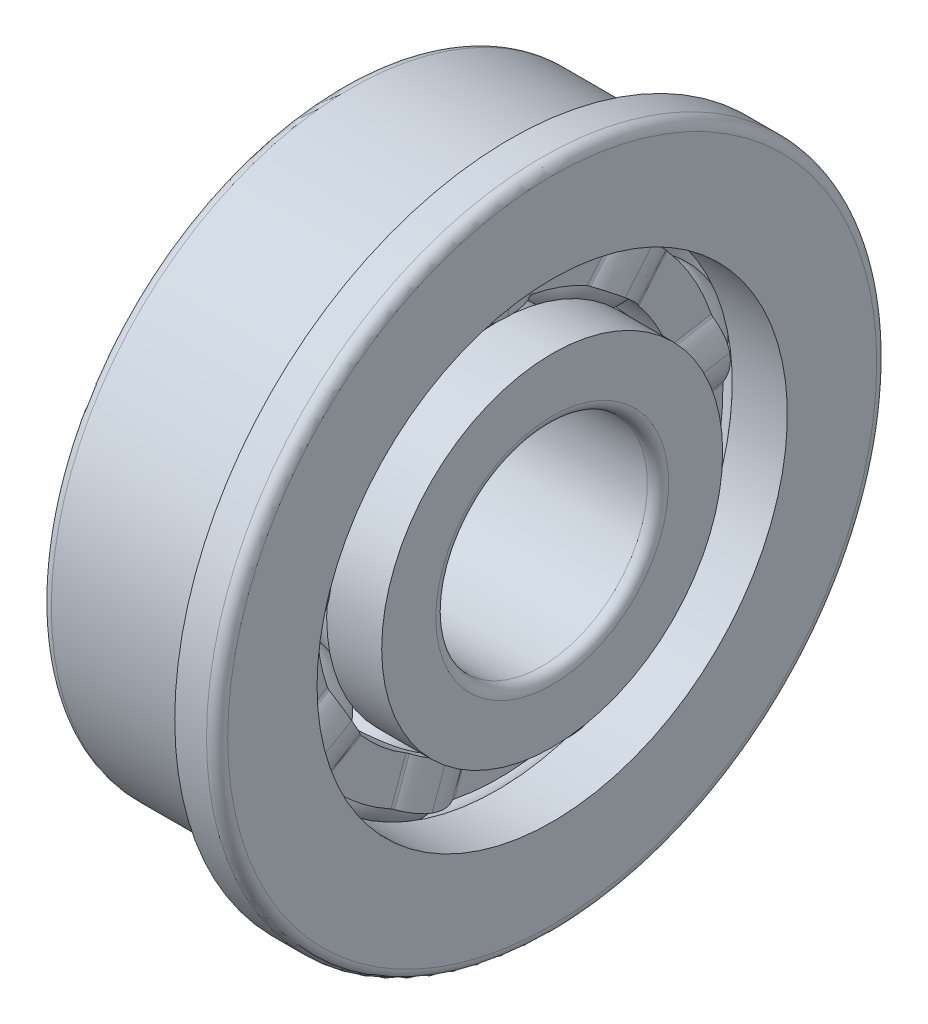
SolidWorks part; units mm, degrees
ref_plane "Front" through (0, 0, 0) normal (0, 0, 1) x (1, 0, 0)
ref_plane "Top" through (0, 0, 0) normal (0, 1, 0) x (1, 0, 0)
ref_plane "Right" through (0, 0, 0) normal (1, 0, 0) x (0, 0, -1)
sketch "Support-Front-Body" plane through (0, 0, 0) normal (0, 0, 1) x (1, 0, 0)
  line L0 (-3, 0) -> (3, 0) construction
  line L1 (3, 0) -> (3, 3) construction
  line L2 (-3, 0) -> (-3, 3) construction
  line L4 (-3, 8.5) -> (3, 8.5)
  line L5 (-3, 8.5) -> (-3, 6.6667)
  line L6 (-3, 6.6667) -> (3, 6.6667)
  line L7 (3, 9.5) -> (3, 6.6667)
  line L8 (-3, 4.8333) -> (3, 4.8333)
  line L9 (-3, 4.8333) -> (-3, 3)
  line L10 (-3, 3) -> (3, 3)
  line L11 (3, 4.8333) -> (3, 3)
  line L13 (-3, 5.75) -> (3, 5.75) construction
  line L14 (0, 0) -> (0, 3) construction
  line L15 (0, 3) -> (0, 4.8333) construction
  line L16 (0, 4.8333) -> (0, 6.6667) construction
  line L17 (0, 6.6667) -> (0, 8.5) construction
  line L19 (1.8, 9.5) -> (3, 9.5)
  line L20 (1.8, 9.5) -> (1.8, 8.5)
  dimension "Diam-Inner" = 6
  dimension "Diam-Outer" = 17
  dimension "CC-Ball" = 11.5
  dimension "Width-Inner" = 6
  dimension "Diam-Flange" = 19
  dimension "Width-Flange" = 1.2
sketch "Support-Front-Ball" plane through (0, 0, 0) normal (0, 0, 1) x (1, 0, 0)
  line L0 (-1.65, 5.75) -> (1.65, 5.75) construction
  line L1 (0, 0) -> (0, 4.1) construction
  line L2 (-3, 5.75) -> (3, 5.75) construction
  line L3 (0, 5.75) -> (0, 7.4) construction
  line L6 (0, 4.1) -> (0, 5.75) construction
  circle A0 centre (0, 5.75) radius 1.65
  dimension "Diam-Ball" = 3.3
sketch "Support-Front-Groove" plane through (0, 0, 0) normal (0, 0, 1) x (1, 0, 0)
  line L0 (0, 6.6667) -> (0, 6.3611) construction
  line L1 (0, 6.3611) -> (0, 6.0556) construction
  line L2 (0, 6.0556) -> (0, 5.75) construction
  line L3 (-3, 5.75) -> (3, 5.75) construction
  line L4 (-1.65, 5.75) -> (1.65, 5.75) construction
  line L6 (-3, 6.6667) -> (3, 6.6667) construction
  line L7 (0, 4.1673) -> (0, 4.1) construction
  line L8 (1.3719, 4.8333) -> (1.4393, 4.8333) construction
  line L9 (-3, 4.8333) -> (3, 4.8333) construction
  line L11 (0, 0) -> (0, 4.1) construction
  line L12 (-1.65, 5.75) -> (1.65, 5.75) construction
  circle A0 centre (0, 5.75) radius 1.65 construction
  circle A1 centre (0, 6.0556) radius 1.8882
  circle A2 centre (0, 5.4444) radius 1.8882
sketch "Support-Front-Ball-Cage" plane through (0, 0, 0) normal (0, 0, 1) x (1, 0, 0)
  line L0 (1.65, 5.75) -> (-1.7681, 5.75) construction
  line L1 (-1.7681, 6.3611) -> (1.7681, 6.3611)
  line L2 (-1.7681, 6.3611) -> (-1.7681, 5.1389)
  line L3 (-1.7681, 5.1389) -> (1.7681, 5.1389)
  line L4 (1.7681, 6.3611) -> (1.7681, 5.1389)
  line L5 (-3, 5.75) -> (3, 5.75) construction
  line L6 (0, 5.1389) -> (0, 6.3611) construction
  line L7 (0, 4.8333) -> (0, 6.6667) construction
  line L8 (1.65, 5.75) -> (1.7681, 5.75) construction
  line L9 (1.709, 5.75) -> (1.709, 6.0556) construction
  line L10 (1.709, 6.0556) -> (1.709, 6.3611) construction
  line L11 (1.709, 6.3611) -> (1.709, 6.6667) construction
  line L12 (-3, 6.6667) -> (3, 6.6667) construction
  line L13 (1.7681, 6.5139) -> (1.4625, 6.5139) construction
  line L14 (0, 6.3611) -> (0, 7.5181) construction
  circle A0 centre (0, 5.75) radius 1.65 construction
  circle A1 centre (0, 5.75) radius 1.7681 construction
  point P26 (1.709, 6.5139)
sketch "Support-Right-Ball-Cage" plane through (0, 0, 0) normal (1, 0, 0) x (0, 0, -1)
  line L0 (0, 0) -> (0, 8.5) construction
  line L1 (0, 0) -> (-5.4637, 6.5114) construction
  line L2 (0, 3.9819) -> (-2.5595, 3.0503) construction
  line L3 (-4.8325, 5.7592) -> (0, 7.5181) construction
  line L4 (0, 0) -> (-3.1968, 7.8759) construction
  line L6 (-2.6137, 8.0882) -> (0, 0) construction
  circle A0 centre (0, 0) radius 5.1389
  circle A1 centre (0, 0) radius 6.3611
  circle A2 centre (0, 5.75) radius 1.7681
  circle A3 centre (0, 0) radius 5.75 construction
  circle A4 centre (-3.696, 4.4048) radius 1.7681
  dimension "Angle-Ball" = 40
ref_plane "Ref-Plane-1" through (0, 3.5161, 1.2798) normal (0, 0.9397, 0.342) x (-1, 0, 0)
sketch "Support-Ball-Gage-Inner" plane through (0, 3.5161, 1.2798) normal (0, 0.9397, 0.342) x (-1, 0, 0)
  line L0 (-1.4787, -0.3427) -> (-1.4787, 0.3427)
  line L1 (1.4787, -0.3427) -> (1.4787, 0.3427)
  line L2 (1.7681, 1.3619) -> (1.7681, -1.3619)
  line L3 (-1.7681, 0) -> (-1.4787, 0) construction
  line L4 (-1.65, -1.9666) -> (-1.65, -0.3427) construction
  line L5 (-1.65, -0.3427) -> (-1.4787, -0.3427) construction
  line L6 (-1.65, -0.3427) -> (-1.65, -0.1713) construction
  line L7 (-1.65, -0.1713) -> (-1.65, 0) construction
  line L8 (-1.4787, 0) -> (0, 0) construction
  line L9 (-1.7681, 1.3619) -> (-1.7681, -1.3619)
  line L10 (-1.7681, -2.1756) -> (-1.7681, -1.7576) construction
  line L11 (-1.65, -0.1713) -> (-1.4787, -0.3427) construction
  line L12 (0, 1.3619) -> (0, -1.3619) construction
  arc A0 (-1.7681, -1.3619) -> (-1.5042, -0.4327) centre (0, -1.3619) cw
  arc A1 (-1.5042, -0.4327) -> (-1.4787, -0.3427) centre (-1.65, -0.3427) ccw
  arc A2 (-1.4787, 0.3427) -> (-1.5042, 0.4327) centre (-1.65, 0.3427) ccw
  arc A3 (-1.5042, 0.4327) -> (-1.7681, 1.3619) centre (0, 1.3619) cw
  arc A4 (1.5042, 0.4327) -> (1.7681, 1.3619) centre (0, 1.3619) ccw
  arc A5 (1.4787, 0.3427) -> (1.5042, 0.4327) centre (1.65, 0.3427) cw
  arc A6 (1.5042, -0.4327) -> (1.4787, -0.3427) centre (1.65, -0.3427) cw
  arc A7 (1.7681, -1.3619) -> (1.5042, -0.4327) centre (0, -1.3619) ccw
  dimension "D1" = 45
ref_plane "Ref-Plane-2" through (0, 6.6386, 2.4163) normal (0, -0.9397, -0.342) x (1, 0, 0)
sketch "Support-Ball-Gage-Outer" plane through (0, 6.6386, 2.4163) normal (0, -0.9397, -0.342) x (1, 0, 0)
  line L0 (1.7681, 2.5713) -> (1.7681, -2.5713)
  line L1 (1.4787, -1.5521) -> (1.4787, 1.5521)
  line L2 (1.7681, 1.3619) -> (1.7681, -1.3619) construction
  line L7 (1.4787, -0.3427) -> (1.4787, 0.3427) construction
  line L8 (0, 2.5713) -> (0, -2.5713) construction
  line L9 (-1.7681, 2.5713) -> (-1.7681, -2.5713)
  line L10 (-1.4787, -1.5521) -> (-1.4787, 1.5521)
  arc A0 (1.7681, -2.5713) -> (1.5042, -1.6421) centre (0, -2.5713) ccw
  arc A1 (1.5042, -1.6421) -> (1.4787, -1.5521) centre (1.65, -1.5521) cw
  arc A2 (1.4787, 1.5521) -> (1.5042, 1.6421) centre (1.65, 1.5521) cw
  arc A3 (1.5042, 1.6421) -> (1.7681, 2.5713) centre (0, 2.5713) ccw
  arc A4 (1.5042, 0.4327) -> (1.4787, 0.3427) centre (1.65, 0.3427) ccw construction
  arc A5 (-1.5042, -1.6421) -> (-1.4787, -1.5521) centre (-1.65, -1.5521) ccw
  arc A6 (-1.7681, -2.5713) -> (-1.5042, -1.6421) centre (0, -2.5713) cw
  arc A7 (-1.5042, 1.6421) -> (-1.7681, 2.5713) centre (0, 2.5713) cw
  arc A8 (-1.4787, 1.5521) -> (-1.5042, 1.6421) centre (-1.65, 1.5521) ccw
ref_axis "Ref-Axis" through (-1.1, 0, 0) along (1, 0, 0)
ref_plane "Ref-Plane-Right" through (3, 0, 0) normal (1, 0, 0) x (0, 0, -1)
ref_plane "Ref-Plane-Left" through (-3, 0, 0) normal (1, 0, 0) x (0, 0, -1)
sketch "Sketch7" plane through (0, 0, 0) normal (0, 0, 1) x (1, 0, 0)
  line L0 (-1.65, 5.75) -> (1.65, 5.75) construction
  line L2 (-1.65, 5.75) -> (1.65, 5.75) construction
  line L4 (-1.65, 5.75) -> (1.65, 5.75)
  circle A0 centre (0, 5.75) radius 1.65 construction
  arc A1 (-1.65, 5.75) -> (1.65, 5.75) centre (0, 5.75) ccw
revolve "Body-Ball" add sketch "Sketch7" angle 360 about L2
sketch "Sketch10" plane through (0, 0, 0) normal (0, 0, 1) x (1, 0, 0)
  line L0 (-3, 0) -> (3, 0) construction
  line L1 (-1.7681, 6.3611) -> (-1.7681, 5.1389) construction
  line L2 (-1.7681, 6.3611) -> (1.7681, 6.3611) construction
  line L3 (1.7681, 6.3611) -> (1.7681, 5.1389) construction
  line L4 (-1.7681, 5.1389) -> (1.7681, 5.1389) construction
  line L5 (-3, 0) -> (3, 0) construction
  line L6 (-1.7681, 6.3611) -> (-1.7681, 5.1389)
  line L7 (-1.7681, 6.3611) -> (1.7681, 6.3611)
  line L8 (1.7681, 6.3611) -> (1.7681, 5.1389)
  line L9 (-1.7681, 5.1389) -> (1.7681, 5.1389)
revolve "Body-Ball-Cage" add sketch "Sketch10" angle 360 about L5
sketch "Sketch16" plane through (0, 3.5161, 1.2798) normal (0, 0.9397, 0.342) x (-1, 0, 0)
  line L0 (1.4787, -0.3427) -> (1.4787, 0.3427) construction
  line L1 (1.7681, 1.3619) -> (1.7681, -1.3619) construction
  line L2 (1.4787, -0.3427) -> (1.4787, 0.3427)
  line L3 (1.7681, 1.3619) -> (1.7681, -1.3619)
  arc A0 (1.5042, 0.4327) -> (1.7681, 1.3619) centre (0, 1.3619) ccw construction
  arc A1 (1.5042, 0.4327) -> (1.4787, 0.3427) centre (1.65, 0.3427) ccw construction
  arc A2 (1.4787, -0.3427) -> (1.5042, -0.4327) centre (1.65, -0.3427) ccw construction
  arc A3 (1.7681, -1.3619) -> (1.5042, -0.4327) centre (0, -1.3619) ccw construction
  arc A4 (1.5042, 0.4327) -> (1.7681, 1.3619) centre (0, 1.3619) ccw
  arc A5 (1.5042, 0.4327) -> (1.4787, 0.3427) centre (1.65, 0.3427) ccw
  arc A6 (1.4787, -0.3427) -> (1.5042, -0.4327) centre (1.65, -0.3427) ccw
  arc A7 (1.7681, -1.3619) -> (1.5042, -0.4327) centre (0, -1.3619) ccw
sketch "Sketch17" plane through (0, 6.6386, 2.4163) normal (0, -0.9397, -0.342) x (1, 0, 0)
  line L0 (-1.4787, -1.5521) -> (-1.4787, 1.5521) construction
  line L1 (-1.7681, 2.5713) -> (-1.7681, -2.5713) construction
  line L2 (-1.4787, -1.5521) -> (-1.4787, 1.5521)
  line L3 (-1.7681, 2.5713) -> (-1.7681, -2.5713)
  arc A0 (-1.7681, 2.5713) -> (-1.5042, 1.6421) centre (0, 2.5713) ccw construction
  arc A1 (-1.4787, 1.5521) -> (-1.5042, 1.6421) centre (-1.65, 1.5521) ccw construction
  arc A2 (-1.5042, -1.6421) -> (-1.4787, -1.5521) centre (-1.65, -1.5521) ccw construction
  arc A3 (-1.5042, -1.6421) -> (-1.7681, -2.5713) centre (0, -2.5713) ccw construction
  arc A4 (-1.7681, 2.5713) -> (-1.5042, 1.6421) centre (0, 2.5713) ccw
  arc A5 (-1.4787, 1.5521) -> (-1.5042, 1.6421) centre (-1.65, 1.5521) ccw
  arc A6 (-1.5042, -1.6421) -> (-1.4787, -1.5521) centre (-1.65, -1.5521) ccw
  arc A7 (-1.5042, -1.6421) -> (-1.7681, -2.5713) centre (0, -2.5713) ccw
loft "Cut-Ball-Cage-1" cut profiles "Sketch16", "Sketch17"
sketch "Sketch14" plane through (0, 3.5161, 1.2798) normal (0, 0.9397, 0.342) x (-1, 0, 0)
  line L0 (-1.4787, -0.3427) -> (-1.4787, 0.3427) construction
  line L1 (-1.7681, 1.3619) -> (-1.7681, -1.3619) construction
  line L2 (-1.4787, -0.3427) -> (-1.4787, 0.3427)
  line L3 (-1.7681, 1.3619) -> (-1.7681, -1.3619)
  arc A0 (-1.7681, 1.3619) -> (-1.5042, 0.4327) centre (0, 1.3619) ccw construction
  arc A1 (-1.4787, 0.3427) -> (-1.5042, 0.4327) centre (-1.65, 0.3427) ccw construction
  arc A2 (-1.5042, -0.4327) -> (-1.4787, -0.3427) centre (-1.65, -0.3427) ccw construction
  arc A3 (-1.5042, -0.4327) -> (-1.7681, -1.3619) centre (0, -1.3619) ccw construction
  arc A4 (-1.7681, 1.3619) -> (-1.5042, 0.4327) centre (0, 1.3619) ccw
  arc A5 (-1.4787, 0.3427) -> (-1.5042, 0.4327) centre (-1.65, 0.3427) ccw
  arc A6 (-1.5042, -0.4327) -> (-1.4787, -0.3427) centre (-1.65, -0.3427) ccw
  arc A7 (-1.5042, -0.4327) -> (-1.7681, -1.3619) centre (0, -1.3619) ccw
sketch "Sketch15" plane through (0, 6.6386, 2.4163) normal (0, -0.9397, -0.342) x (1, 0, 0)
  line L0 (1.4787, -1.5521) -> (1.4787, 1.5521) construction
  line L1 (1.7681, 2.5713) -> (1.7681, -2.5713) construction
  line L2 (1.4787, -1.5521) -> (1.4787, 1.5521)
  line L3 (1.7681, 2.5713) -> (1.7681, -2.5713)
  arc A0 (1.5042, 1.6421) -> (1.7681, 2.5713) centre (0, 2.5713) ccw construction
  arc A1 (1.5042, 1.6421) -> (1.4787, 1.5521) centre (1.65, 1.5521) ccw construction
  arc A2 (1.4787, -1.5521) -> (1.5042, -1.6421) centre (1.65, -1.5521) ccw construction
  arc A3 (1.7681, -2.5713) -> (1.5042, -1.6421) centre (0, -2.5713) ccw construction
  arc A4 (1.5042, 1.6421) -> (1.7681, 2.5713) centre (0, 2.5713) ccw
  arc A5 (1.5042, 1.6421) -> (1.4787, 1.5521) centre (1.65, 1.5521) ccw
  arc A6 (1.4787, -1.5521) -> (1.5042, -1.6421) centre (1.65, -1.5521) ccw
  arc A7 (1.7681, -2.5713) -> (1.5042, -1.6421) centre (0, -2.5713) ccw
loft "Cut-Ball-Cage-2" cut profiles "Sketch15", "Sketch14"
pattern_circular "Pattern-Ball" count 9 over 360 about axis through (-1.1, 0, 0) along (1, 0, 0) of "Body-Ball", "Cut-Ball-Cage-2", "Cut-Ball-Cage-1"
sketch "Sketch2" plane through (0, 0, 0) normal (0, 0, 1) x (1, 0, 0)
  line L4 (-3, 4.8333) -> (-3, 3) construction
  line L5 (-3, 4.8333) -> (3, 4.8333) construction
  line L6 (3, 4.8333) -> (3, 3) construction
  line L7 (-3, 3) -> (3, 3) construction
  line L8 (-3, 0) -> (3, 0) construction
  line L9 (-3, 0) -> (3, 0) construction
  line L10 (-3, 4.8333) -> (-3, 3)
  line L11 (-3, 4.8333) -> (-1.4393, 4.8333)
  line L12 (3, 4.8333) -> (3, 3)
  line L13 (-3, 3) -> (3, 3)
  line L14 (1.4393, 4.8333) -> (3, 4.8333)
  circle A1 centre (0, 6.0556) radius 1.8882 construction
  arc A2 (-1.4393, 4.8333) -> (1.4393, 4.8333) centre (0, 6.0556) ccw
sketch "Sketch8" plane through (0, 0, 0) normal (0, 0, 1) x (1, 0, 0)
  line L0 (-3, 0) -> (3, 0) construction
  line L1 (-3, 8.5) -> (-3, 6.6667) construction
  line L2 (-3, 6.6667) -> (3, 6.6667) construction
  line L4 (-3, 0) -> (3, 0) construction
  line L5 (1.8, 9.5) -> (1.8, 8.5) construction
  line L6 (1.8, 9.5) -> (3, 9.5) construction
  line L8 (1.8, 9.5) -> (1.8, 8.5)
  line L10 (-3, 8.5) -> (-3, 6.6667)
  line L11 (-3, 6.6667) -> (-1.4393, 6.6667)
  line L12 (3, 9.5) -> (3, 6.6667) construction
  line L13 (-3, 8.5) -> (3, 8.5) construction
  line L14 (1.4393, 6.6667) -> (3, 6.6667)
  line L15 (1.8, 9.5) -> (3, 9.5)
  line L16 (3, 9.5) -> (3, 6.6667)
  line L17 (-3, 8.5) -> (1.8, 8.5)
  circle A1 centre (0, 5.4444) radius 1.8882 construction
  arc A2 (1.4393, 6.6667) -> (-1.4393, 6.6667) centre (0, 5.4444) ccw
revolve "Body-Inner" add sketch "Sketch2" angle 360 about L9
revolve "Body-Outer" add sketch "Sketch8" angle 360 about L4
fillet "Cosmetic-Fillet-Outer-1" radius 0.3 1 edges at (-3, 0, 8.5)
fillet "Cosmetic-Fillet-Outer-2" radius 0.3 1 edges at (3, 0, 9.5)
fillet "Cosmetic-Fillet-Inner-1" radius 0.3 1 edges at (-3, 0, 3)
fillet "Cosmetic-Fillet-Inner-2" radius 0.3 1 edges at (3, 0, 3)
equation "\"Diam-Ball@Support-Front-Ball\"=(((\"Diam-Outer@Support-Front-Body\"-\"Diam-Inner@Support-Front-Body\")/2)*3)/5"
equation "\"Num-Ball@Pattern-Ball\"=INT((PI*(\"Diam-Outer@Support-Front-Body\"-((\"Diam-Outer@Support-Front-Body\"-\"Diam-Inner@Support-Front-Body\")/2)))/(\"Diam-Ball@Support-Front-Ball\"*1.2))"
equation "\"Angle-Ball@Support-Right-Ball-Cage\" = 360 / INT(((PI*(\"Diam-Outer@Support-Front-Body\"-((\"Diam-Outer@Support-Front-Body\"-\"Diam-Inner@Support-Front-Body\")/4)))/2)/\"Diam-Ball@Support-Front-Ball\")"
equation "\"Angle-Ball@Support-Right-Ball-Cage\" = 360 / \"Num-Ball@Pattern-Ball\""
